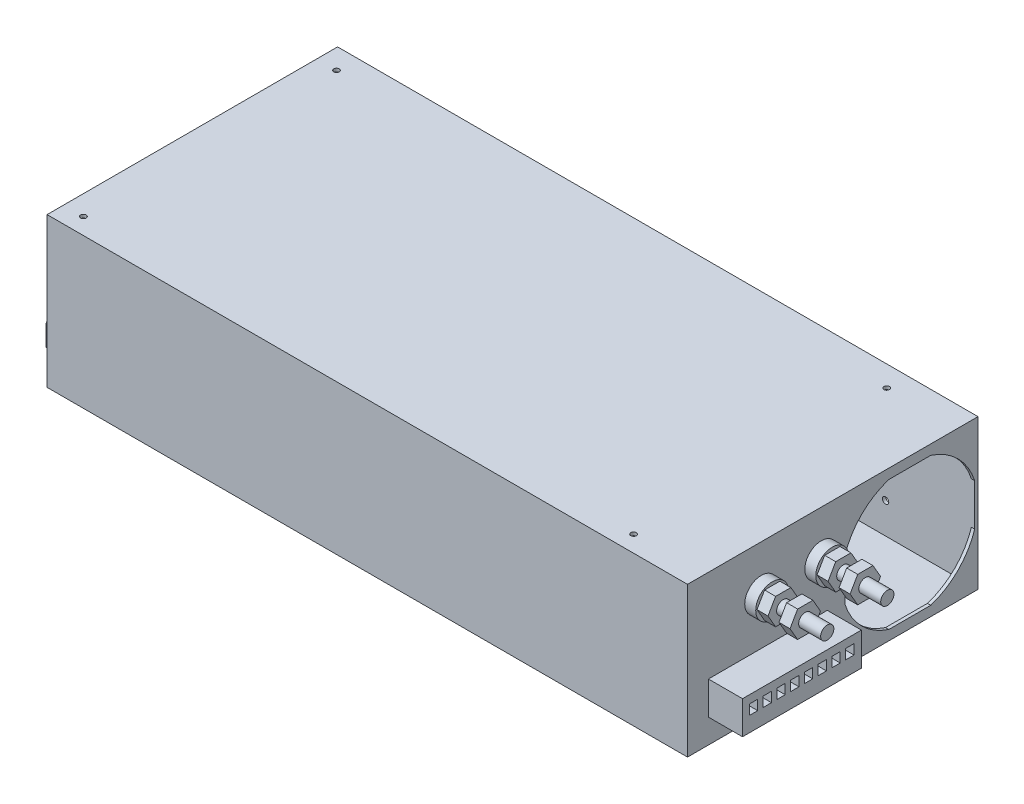
SolidWorks part; units mm, degrees
ref_plane "Front Plane" through (0, 0, 0) normal (0, 0, 1) x (1, 0, 0)
ref_plane "Top Plane" through (0, 0, 0) normal (0, 1, 0) x (1, 0, 0)
ref_plane "Right Plane" through (0, 0, 0) normal (1, 0, 0) x (0, 0, -1)
sketch "Sketch1" plane through (0, 0, 0) normal (0, 1, 0) x (1, 0, 0)
  line L1 (-145.5, -66) -> (145.5, -66)
  line L2 (-145.5, -66) -> (-145.5, 66)
  line L3 (-145.5, 66) -> (145.5, 66)
  line L4 (145.5, -66) -> (145.5, 66)
  line L5 (0, 66) -> (0, -66) construction
  line L6 (-145.5, 0) -> (145.5, 0) construction
  line L7 (-136.5, 56.5) -> (113.5, 56.5) construction
  line L8 (-136.5, 56.5) -> (-136.5, -58.5) construction
  line L9 (-136.5, -58.5) -> (113.5, -58.5) construction
  line L10 (113.5, 56.5) -> (113.5, -58.5) construction
  line L11 (-11.5, -58.5) -> (-11.5, 56.5) construction
  line L12 (-136.5, -1) -> (113.5, -1) construction
  circle A0 centre (-136.5, 56.5) radius 1.5 construction
  circle A1 centre (113.5, 56.5) radius 1.5 construction
  circle A2 centre (113.5, -58.5) radius 1.5 construction
  circle A3 centre (-136.5, -58.5) radius 1.5 construction
  point P0 (0, 0)
  point P181 (-11.5, -1)
  dimension "D3" = 32
  dimension "D4" = 3
  dimension "D6" = 250
  dimension "D7" = 115
  dimension "D1" = 291
  dimension "D2" = 132
  dimension "D5" = 9.5
extrude "Boss-Extrude1" add sketch "Sketch1" along normal blind 68
sketch "Sketch2" plane through (0, 0, 0) normal (0, -1, 0) x (-1, 0, 0)
  line L0 (-50.3392, -42.885) -> (382.3274, -42.885) construction
  line L1 (-49.7856, -55.3048) -> (382.8811, -55.3048) construction
sketch "Sketch4" plane through (145.5, 0, 0) normal (1, 0, 0) x (0, 0, -1)
  line L0 (-7.9676, 299.7952) -> (184.6991, 299.7952) construction
sketch "Sketch5" plane through (-145.5, 0, 0) normal (-1, 0, 0) x (0, 0, 1)
  line L0 (404.3119, 214.2342) -> (558.9785, 214.2342) construction
sketch "Sketch6" plane through (0, 0, -66) normal (0, 0, -1) x (-1, 0, 0)
  line L0 (145.5, 34) -> (-145.5, 34) construction
  line L1 (145.5, 68) -> (145.5, 0) construction
  line L2 (-145.5, 68) -> (-145.5, 0) construction
  line L3 (-145.5, 68) -> (145.5, 68) construction
  line L4 (-95, 15.5) -> (104.5, 15.5) construction
  line L5 (-95, 15.5) -> (-95, 52.5) construction
  line L6 (-95, 52.5) -> (104.5, 52.5) construction
  line L7 (104.5, 15.5) -> (104.5, 52.5) construction
  line L8 (4.75, 52.5) -> (4.75, 15.5) construction
  line L9 (-95, 34) -> (104.5, 34) construction
  point P6 (4.75, 34)
  point P12 (95, 52.5)
  point P13 (95, 15.5)
  point P17 (-105, 52.5)
  point P18 (-105, 15.5)
  dimension "D1" = 15.5
  dimension "D2" = 41
  dimension "D3" = 199.5
  dimension "D4" = 50.5
  dimension "D6" = 200
  dimension "D5" = 2
shell "Shell1" thickness 1.5
hole_wizard "M3x0.5 Tapped Hole1" positions "Sketch8" profile "Sketch9" tap size "M3x0.5" standard "ANSI Metric"
sketch "Sketch8" plane through (0, 68, 0) normal (0, 1, 0) x (1, 0, 0)
  point P0 (-136.5, 56.5)
  point P3 (-136.5, -58.5)
  point P6 (113.5, -58.5)
  point P9 (113.5, 56.5)
sketch "Sketch9" plane through (-136.5, 68, -56.5) normal (1, 0, 0) x (0, 0, 1)
  line L0 (0, 0) -> (0, 8.2511)
  line L1 (0, 8.2511) -> (1.25, 7.5)
  line L2 (1.25, 7.5) -> (1.25, 0)
  line L5 (1.25, 0) -> (0, 0)
  line L10 (0, 8.2511) -> (-1.25, 7.5) construction
  line L11 (0, -6.35) -> (0, 107.95) construction
  dimension "Tap Drill Dia." = 2.5
  dimension "Tap Drill Depth" = 7.5
  dimension "Drill Angle" = 118
cosmetic thread "Hole Thread1" parameters "D1"=1.5, "D2"=3
cosmetic thread "Hole Thread2" parameters "D1"=1.5, "D2"=3
cosmetic thread "Hole Thread3" parameters "D1"=1.5, "D2"=3
cosmetic thread "Hole Thread4" parameters "D1"=1.5, "D2"=3
sketch "Sketch10" plane through (0, 0, 0) normal (0, -1, 0) x (1, 0, 0)
  line L0 (-131.25, -60.5) -> (-115.25, -60.5) construction
  line L1 (-131.25, -59) -> (-115.25, -59)
  line L2 (-131.25, -62) -> (-115.25, -62)
  line L3 (-145.5, -66) -> (145.5, -66) construction
  line L4 (-145.5, 66) -> (-145.5, -66) construction
  line L5 (-104.75, -60.5) -> (-88.75, -60.5) construction
  line L6 (-104.75, -59) -> (-88.75, -59)
  line L7 (-104.75, -62) -> (-88.75, -62)
  line L8 (-104.75, -55.5) -> (-88.75, -55.5) construction
  line L9 (-104.75, -54) -> (-88.75, -54)
  line L10 (-104.75, -57) -> (-88.75, -57)
  line L11 (-104.75, -50.5) -> (-88.75, -50.5) construction
  line L12 (-104.75, -49) -> (-88.75, -49)
  line L13 (-104.75, -52) -> (-88.75, -52)
  line L14 (-104.75, -45.5) -> (-88.75, -45.5) construction
  line L15 (-104.75, -44) -> (-88.75, -44)
  line L16 (-104.75, -47) -> (-88.75, -47)
  line L17 (-104.75, -40.5) -> (-88.75, -40.5) construction
  line L18 (-104.75, -39) -> (-88.75, -39)
  line L19 (-104.75, -42) -> (-88.75, -42)
  line L20 (-104.75, -35.5) -> (-88.75, -35.5) construction
  line L21 (-104.75, -34) -> (-88.75, -34)
  line L22 (-104.75, -37) -> (-88.75, -37)
  line L23 (-104.75, -30.5) -> (-88.75, -30.5) construction
  line L24 (-104.75, -29) -> (-88.75, -29)
  line L25 (-104.75, -32) -> (-88.75, -32)
  line L26 (-104.75, -25.5) -> (-88.75, -25.5) construction
  line L27 (-104.75, -24) -> (-88.75, -24)
  line L28 (-104.75, -27) -> (-88.75, -27)
  line L29 (-104.75, -20.5) -> (-88.75, -20.5) construction
  line L30 (-104.75, -19) -> (-88.75, -19)
  line L31 (-104.75, -22) -> (-88.75, -22)
  line L32 (-104.75, -15.5) -> (-88.75, -15.5) construction
  line L33 (-104.75, -14) -> (-88.75, -14)
  line L34 (-104.75, -17) -> (-88.75, -17)
  line L35 (-104.75, -10.5) -> (-88.75, -10.5) construction
  line L36 (-104.75, -9) -> (-88.75, -9)
  line L37 (-104.75, -12) -> (-88.75, -12)
  line L38 (-104.75, -5.5) -> (-88.75, -5.5) construction
  line L39 (-104.75, -4) -> (-88.75, -4)
  line L40 (-104.75, -7) -> (-88.75, -7)
  line L41 (-104.75, -0.5) -> (-88.75, -0.5) construction
  line L42 (-104.75, 1) -> (-88.75, 1)
  line L43 (-104.75, -2) -> (-88.75, -2)
  line L44 (-104.75, 4.5) -> (-88.75, 4.5) construction
  line L45 (-104.75, 6) -> (-88.75, 6)
  line L46 (-104.75, 3) -> (-88.75, 3)
  line L47 (-104.75, 9.5) -> (-88.75, 9.5) construction
  line L48 (-104.75, 11) -> (-88.75, 11)
  line L49 (-104.75, 8) -> (-88.75, 8)
  line L50 (-104.75, 14.5) -> (-88.75, 14.5) construction
  line L51 (-104.75, 16) -> (-88.75, 16)
  line L52 (-104.75, 13) -> (-88.75, 13)
  line L53 (-104.75, 19.5) -> (-88.75, 19.5) construction
  line L54 (-104.75, 21) -> (-88.75, 21)
  line L55 (-104.75, 18) -> (-88.75, 18)
  line L56 (-104.75, 24.5) -> (-88.75, 24.5) construction
  line L57 (-104.75, 26) -> (-88.75, 26)
  line L58 (-104.75, 23) -> (-88.75, 23)
  line L59 (-104.75, 29.5) -> (-88.75, 29.5) construction
  line L60 (-104.75, 31) -> (-88.75, 31)
  line L61 (-104.75, 28) -> (-88.75, 28)
  line L62 (-104.75, 34.5) -> (-88.75, 34.5) construction
  line L63 (-104.75, 36) -> (-88.75, 36)
  line L64 (-104.75, 33) -> (-88.75, 33)
  line L65 (-104.75, 39.5) -> (-88.75, 39.5) construction
  line L66 (-104.75, 41) -> (-88.75, 41)
  line L67 (-104.75, 38) -> (-88.75, 38)
  line L68 (-104.75, 44.5) -> (-88.75, 44.5) construction
  line L69 (-104.75, 46) -> (-88.75, 46)
  line L70 (-104.75, 43) -> (-88.75, 43)
  line L71 (-104.75, 49.5) -> (-88.75, 49.5) construction
  line L72 (-104.75, 51) -> (-88.75, 51)
  line L73 (-104.75, 48) -> (-88.75, 48)
  line L74 (-104.75, 54.5) -> (-88.75, 54.5) construction
  line L75 (-104.75, 56) -> (-88.75, 56)
  line L76 (-104.75, 53) -> (-88.75, 53)
  line L77 (-104.75, 59.5) -> (-88.75, 59.5) construction
  line L78 (-104.75, 61) -> (-88.75, 61)
  line L79 (-104.75, 58) -> (-88.75, 58)
  line L80 (-131.25, -55.5) -> (-115.25, -55.5) construction
  line L81 (-131.25, -54) -> (-115.25, -54)
  line L82 (-131.25, -57) -> (-115.25, -57)
  line L83 (-131.25, -50.5) -> (-115.25, -50.5) construction
  line L84 (-131.25, -49) -> (-115.25, -49)
  line L85 (-131.25, -52) -> (-115.25, -52)
  line L86 (-131.25, -45.5) -> (-115.25, -45.5) construction
  line L87 (-131.25, -44) -> (-115.25, -44)
  line L88 (-131.25, -47) -> (-115.25, -47)
  line L89 (-131.25, -40.5) -> (-115.25, -40.5) construction
  line L90 (-131.25, -39) -> (-115.25, -39)
  line L91 (-131.25, -42) -> (-115.25, -42)
  line L92 (-131.25, -35.5) -> (-115.25, -35.5) construction
  line L93 (-131.25, -34) -> (-115.25, -34)
  line L94 (-131.25, -37) -> (-115.25, -37)
  line L95 (-131.25, -30.5) -> (-115.25, -30.5) construction
  line L96 (-131.25, -29) -> (-115.25, -29)
  line L97 (-131.25, -32) -> (-115.25, -32)
  line L98 (-131.25, -25.5) -> (-115.25, -25.5) construction
  line L99 (-131.25, -24) -> (-115.25, -24)
  line L100 (-131.25, -27) -> (-115.25, -27)
  line L101 (-131.25, -20.5) -> (-115.25, -20.5) construction
  line L102 (-131.25, -19) -> (-115.25, -19)
  line L103 (-131.25, -22) -> (-115.25, -22)
  line L104 (-131.25, -15.5) -> (-115.25, -15.5) construction
  line L105 (-131.25, -14) -> (-115.25, -14)
  line L106 (-131.25, -17) -> (-115.25, -17)
  line L107 (-131.25, -10.5) -> (-115.25, -10.5) construction
  line L108 (-131.25, -9) -> (-115.25, -9)
  line L109 (-131.25, -12) -> (-115.25, -12)
  line L110 (-131.25, -5.5) -> (-115.25, -5.5) construction
  line L111 (-131.25, -4) -> (-115.25, -4)
  line L112 (-131.25, -7) -> (-115.25, -7)
  line L113 (-131.25, -0.5) -> (-115.25, -0.5) construction
  line L114 (-131.25, 1) -> (-115.25, 1)
  line L115 (-131.25, -2) -> (-115.25, -2)
  line L116 (-131.25, 4.5) -> (-115.25, 4.5) construction
  line L117 (-131.25, 6) -> (-115.25, 6)
  line L118 (-131.25, 3) -> (-115.25, 3)
  line L119 (-131.25, 9.5) -> (-115.25, 9.5) construction
  line L120 (-131.25, 11) -> (-115.25, 11)
  line L121 (-131.25, 8) -> (-115.25, 8)
  line L122 (-131.25, 14.5) -> (-115.25, 14.5) construction
  line L123 (-131.25, 16) -> (-115.25, 16)
  line L124 (-131.25, 13) -> (-115.25, 13)
  line L125 (-131.25, 19.5) -> (-115.25, 19.5) construction
  line L126 (-131.25, 21) -> (-115.25, 21)
  line L127 (-131.25, 18) -> (-115.25, 18)
  line L128 (-131.25, 24.5) -> (-115.25, 24.5) construction
  line L129 (-131.25, 26) -> (-115.25, 26)
  line L130 (-131.25, 23) -> (-115.25, 23)
  line L131 (-131.25, 29.5) -> (-115.25, 29.5) construction
  line L132 (-131.25, 31) -> (-115.25, 31)
  line L133 (-131.25, 28) -> (-115.25, 28)
  line L134 (-131.25, 34.5) -> (-115.25, 34.5) construction
  line L135 (-131.25, 36) -> (-115.25, 36)
  line L136 (-131.25, 33) -> (-115.25, 33)
  line L137 (-131.25, 39.5) -> (-115.25, 39.5) construction
  line L138 (-131.25, 41) -> (-115.25, 41)
  line L139 (-131.25, 38) -> (-115.25, 38)
  line L140 (-131.25, 44.5) -> (-115.25, 44.5) construction
  line L141 (-131.25, 46) -> (-115.25, 46)
  line L142 (-131.25, 43) -> (-115.25, 43)
  line L143 (-131.25, 49.5) -> (-115.25, 49.5) construction
  line L144 (-131.25, 51) -> (-115.25, 51)
  line L145 (-131.25, 48) -> (-115.25, 48)
  line L146 (-131.25, 54.5) -> (-115.25, 54.5) construction
  line L147 (-131.25, 56) -> (-115.25, 56)
  line L148 (-131.25, 53) -> (-115.25, 53)
  line L149 (-131.25, 59.5) -> (-115.25, 59.5) construction
  line L150 (-131.25, 61) -> (-115.25, 61)
  line L151 (-131.25, 58) -> (-115.25, 58)
  arc A0 (-131.25, -59) -> (-131.25, -62) centre (-131.25, -60.5) ccw
  arc A1 (-115.25, -62) -> (-115.25, -59) centre (-115.25, -60.5) ccw
  arc A2 (-104.75, -59) -> (-104.75, -62) centre (-104.75, -60.5) ccw
  arc A3 (-88.75, -62) -> (-88.75, -59) centre (-88.75, -60.5) ccw
  arc A4 (-104.75, -54) -> (-104.75, -57) centre (-104.75, -55.5) ccw
  arc A5 (-88.75, -57) -> (-88.75, -54) centre (-88.75, -55.5) ccw
  arc A6 (-104.75, -49) -> (-104.75, -52) centre (-104.75, -50.5) ccw
  arc A7 (-88.75, -52) -> (-88.75, -49) centre (-88.75, -50.5) ccw
  arc A8 (-104.75, -44) -> (-104.75, -47) centre (-104.75, -45.5) ccw
  arc A9 (-88.75, -47) -> (-88.75, -44) centre (-88.75, -45.5) ccw
  arc A10 (-104.75, -39) -> (-104.75, -42) centre (-104.75, -40.5) ccw
  arc A11 (-88.75, -42) -> (-88.75, -39) centre (-88.75, -40.5) ccw
  arc A12 (-104.75, -34) -> (-104.75, -37) centre (-104.75, -35.5) ccw
  arc A13 (-88.75, -37) -> (-88.75, -34) centre (-88.75, -35.5) ccw
  arc A14 (-104.75, -29) -> (-104.75, -32) centre (-104.75, -30.5) ccw
  arc A15 (-88.75, -32) -> (-88.75, -29) centre (-88.75, -30.5) ccw
  arc A16 (-104.75, -24) -> (-104.75, -27) centre (-104.75, -25.5) ccw
  arc A17 (-88.75, -27) -> (-88.75, -24) centre (-88.75, -25.5) ccw
  arc A18 (-104.75, -19) -> (-104.75, -22) centre (-104.75, -20.5) ccw
  arc A19 (-88.75, -22) -> (-88.75, -19) centre (-88.75, -20.5) ccw
  arc A20 (-104.75, -14) -> (-104.75, -17) centre (-104.75, -15.5) ccw
  arc A21 (-88.75, -17) -> (-88.75, -14) centre (-88.75, -15.5) ccw
  arc A22 (-104.75, -9) -> (-104.75, -12) centre (-104.75, -10.5) ccw
  arc A23 (-88.75, -12) -> (-88.75, -9) centre (-88.75, -10.5) ccw
  arc A24 (-104.75, -4) -> (-104.75, -7) centre (-104.75, -5.5) ccw
  arc A25 (-88.75, -7) -> (-88.75, -4) centre (-88.75, -5.5) ccw
  arc A26 (-104.75, 1) -> (-104.75, -2) centre (-104.75, -0.5) ccw
  arc A27 (-88.75, -2) -> (-88.75, 1) centre (-88.75, -0.5) ccw
  arc A28 (-104.75, 6) -> (-104.75, 3) centre (-104.75, 4.5) ccw
  arc A29 (-88.75, 3) -> (-88.75, 6) centre (-88.75, 4.5) ccw
  arc A30 (-104.75, 11) -> (-104.75, 8) centre (-104.75, 9.5) ccw
  arc A31 (-88.75, 8) -> (-88.75, 11) centre (-88.75, 9.5) ccw
  arc A32 (-104.75, 16) -> (-104.75, 13) centre (-104.75, 14.5) ccw
  arc A33 (-88.75, 13) -> (-88.75, 16) centre (-88.75, 14.5) ccw
  arc A34 (-104.75, 21) -> (-104.75, 18) centre (-104.75, 19.5) ccw
  arc A35 (-88.75, 18) -> (-88.75, 21) centre (-88.75, 19.5) ccw
  arc A36 (-104.75, 26) -> (-104.75, 23) centre (-104.75, 24.5) ccw
  arc A37 (-88.75, 23) -> (-88.75, 26) centre (-88.75, 24.5) ccw
  arc A38 (-104.75, 31) -> (-104.75, 28) centre (-104.75, 29.5) ccw
  arc A39 (-88.75, 28) -> (-88.75, 31) centre (-88.75, 29.5) ccw
  arc A40 (-104.75, 36) -> (-104.75, 33) centre (-104.75, 34.5) ccw
  arc A41 (-88.75, 33) -> (-88.75, 36) centre (-88.75, 34.5) ccw
  arc A42 (-104.75, 41) -> (-104.75, 38) centre (-104.75, 39.5) ccw
  arc A43 (-88.75, 38) -> (-88.75, 41) centre (-88.75, 39.5) ccw
  arc A44 (-104.75, 46) -> (-104.75, 43) centre (-104.75, 44.5) ccw
  arc A45 (-88.75, 43) -> (-88.75, 46) centre (-88.75, 44.5) ccw
  arc A46 (-104.75, 51) -> (-104.75, 48) centre (-104.75, 49.5) ccw
  arc A47 (-88.75, 48) -> (-88.75, 51) centre (-88.75, 49.5) ccw
  arc A48 (-104.75, 56) -> (-104.75, 53) centre (-104.75, 54.5) ccw
  arc A49 (-88.75, 53) -> (-88.75, 56) centre (-88.75, 54.5) ccw
  arc A50 (-104.75, 61) -> (-104.75, 58) centre (-104.75, 59.5) ccw
  arc A51 (-88.75, 58) -> (-88.75, 61) centre (-88.75, 59.5) ccw
  arc A52 (-131.25, -54) -> (-131.25, -57) centre (-131.25, -55.5) ccw
  arc A53 (-115.25, -57) -> (-115.25, -54) centre (-115.25, -55.5) ccw
  arc A54 (-131.25, -49) -> (-131.25, -52) centre (-131.25, -50.5) ccw
  arc A55 (-115.25, -52) -> (-115.25, -49) centre (-115.25, -50.5) ccw
  arc A56 (-131.25, -44) -> (-131.25, -47) centre (-131.25, -45.5) ccw
  arc A57 (-115.25, -47) -> (-115.25, -44) centre (-115.25, -45.5) ccw
  arc A58 (-131.25, -39) -> (-131.25, -42) centre (-131.25, -40.5) ccw
  arc A59 (-115.25, -42) -> (-115.25, -39) centre (-115.25, -40.5) ccw
  arc A60 (-131.25, -34) -> (-131.25, -37) centre (-131.25, -35.5) ccw
  arc A61 (-115.25, -37) -> (-115.25, -34) centre (-115.25, -35.5) ccw
  arc A62 (-131.25, -29) -> (-131.25, -32) centre (-131.25, -30.5) ccw
  arc A63 (-115.25, -32) -> (-115.25, -29) centre (-115.25, -30.5) ccw
  arc A64 (-131.25, -24) -> (-131.25, -27) centre (-131.25, -25.5) ccw
  arc A65 (-115.25, -27) -> (-115.25, -24) centre (-115.25, -25.5) ccw
  arc A66 (-131.25, -19) -> (-131.25, -22) centre (-131.25, -20.5) ccw
  arc A67 (-115.25, -22) -> (-115.25, -19) centre (-115.25, -20.5) ccw
  arc A68 (-131.25, -14) -> (-131.25, -17) centre (-131.25, -15.5) ccw
  arc A69 (-115.25, -17) -> (-115.25, -14) centre (-115.25, -15.5) ccw
  arc A70 (-131.25, -9) -> (-131.25, -12) centre (-131.25, -10.5) ccw
  arc A71 (-115.25, -12) -> (-115.25, -9) centre (-115.25, -10.5) ccw
  arc A72 (-131.25, -4) -> (-131.25, -7) centre (-131.25, -5.5) ccw
  arc A73 (-115.25, -7) -> (-115.25, -4) centre (-115.25, -5.5) ccw
  arc A74 (-131.25, 1) -> (-131.25, -2) centre (-131.25, -0.5) ccw
  arc A75 (-115.25, -2) -> (-115.25, 1) centre (-115.25, -0.5) ccw
  arc A76 (-131.25, 6) -> (-131.25, 3) centre (-131.25, 4.5) ccw
  arc A77 (-115.25, 3) -> (-115.25, 6) centre (-115.25, 4.5) ccw
  arc A78 (-131.25, 11) -> (-131.25, 8) centre (-131.25, 9.5) ccw
  arc A79 (-115.25, 8) -> (-115.25, 11) centre (-115.25, 9.5) ccw
  arc A80 (-131.25, 16) -> (-131.25, 13) centre (-131.25, 14.5) ccw
  arc A81 (-115.25, 13) -> (-115.25, 16) centre (-115.25, 14.5) ccw
  arc A82 (-131.25, 21) -> (-131.25, 18) centre (-131.25, 19.5) ccw
  arc A83 (-115.25, 18) -> (-115.25, 21) centre (-115.25, 19.5) ccw
  arc A84 (-131.25, 26) -> (-131.25, 23) centre (-131.25, 24.5) ccw
  arc A85 (-115.25, 23) -> (-115.25, 26) centre (-115.25, 24.5) ccw
  arc A86 (-131.25, 31) -> (-131.25, 28) centre (-131.25, 29.5) ccw
  arc A87 (-115.25, 28) -> (-115.25, 31) centre (-115.25, 29.5) ccw
  arc A88 (-131.25, 36) -> (-131.25, 33) centre (-131.25, 34.5) ccw
  arc A89 (-115.25, 33) -> (-115.25, 36) centre (-115.25, 34.5) ccw
  arc A90 (-131.25, 41) -> (-131.25, 38) centre (-131.25, 39.5) ccw
  arc A91 (-115.25, 38) -> (-115.25, 41) centre (-115.25, 39.5) ccw
  arc A92 (-131.25, 46) -> (-131.25, 43) centre (-131.25, 44.5) ccw
  arc A93 (-115.25, 43) -> (-115.25, 46) centre (-115.25, 44.5) ccw
  arc A94 (-131.25, 51) -> (-131.25, 48) centre (-131.25, 49.5) ccw
  arc A95 (-115.25, 48) -> (-115.25, 51) centre (-115.25, 49.5) ccw
  arc A96 (-131.25, 56) -> (-131.25, 53) centre (-131.25, 54.5) ccw
  arc A97 (-115.25, 53) -> (-115.25, 56) centre (-115.25, 54.5) ccw
  arc A98 (-131.25, 61) -> (-131.25, 58) centre (-131.25, 59.5) ccw
  arc A99 (-115.25, 58) -> (-115.25, 61) centre (-115.25, 59.5) ccw
  point P2 (-123.25, -60.5)
  point P15 (-96.75, -60.5)
  point P22 (-96.75, -55.5)
  point P29 (-96.75, -50.5)
  point P36 (-96.75, -45.5)
  point P43 (-96.75, -40.5)
  point P50 (-96.75, -35.5)
  point P57 (-96.75, -30.5)
  point P64 (-96.75, -25.5)
  point P71 (-96.75, -20.5)
  point P78 (-96.75, -15.5)
  point P85 (-96.75, -10.5)
  point P92 (-96.75, -5.5)
  point P99 (-96.75, -0.5)
  point P106 (-96.75, 4.5)
  point P113 (-96.75, 9.5)
  point P120 (-96.75, 14.5)
  point P127 (-96.75, 19.5)
  point P134 (-96.75, 24.5)
  point P141 (-96.75, 29.5)
  point P148 (-96.75, 34.5)
  point P155 (-96.75, 39.5)
  point P162 (-96.75, 44.5)
  point P169 (-96.75, 49.5)
  point P176 (-96.75, 54.5)
  point P183 (-96.75, 59.5)
  point P190 (-123.25, -55.5)
  point P197 (-123.25, -50.5)
  point P204 (-123.25, -45.5)
  point P211 (-123.25, -40.5)
  point P218 (-123.25, -35.5)
  point P225 (-123.25, -30.5)
  point P232 (-123.25, -25.5)
  point P239 (-123.25, -20.5)
  point P246 (-123.25, -15.5)
  point P253 (-123.25, -10.5)
  point P260 (-123.25, -5.5)
  point P267 (-123.25, -0.5)
  point P274 (-123.25, 4.5)
  point P281 (-123.25, 9.5)
  point P288 (-123.25, 14.5)
  point P295 (-123.25, 19.5)
  point P302 (-123.25, 24.5)
  point P309 (-123.25, 29.5)
  point P316 (-123.25, 34.5)
  point P323 (-123.25, 39.5)
  point P330 (-123.25, 44.5)
  point P337 (-123.25, 49.5)
  point P344 (-123.25, 54.5)
  point P351 (-123.25, 59.5)
  dimension "D1" = 1.5
  dimension "D7" = 26.5
  dimension "D8" = 5
  dimension "D2" = 16
  dimension "D3" = 5.5
  dimension "D4" = 14.25
  dimension "D5" = 2
  dimension "D6" = 25
extrude "Cut-Extrude1" cut sketch "Sketch10" against normal up to next (1.5 mm away)
sketch "Sketch11" plane through (-145.5, 0, 0) normal (-1, 0, 0) x (0, 0, 1)
  line L0 (-66, 0) -> (66, 0) construction
  line L1 (60, 10) -> (50, 10)
  line L2 (60, 10) -> (60, 21.5)
  line L3 (60, 21.5) -> (50, 21.5)
  line L4 (50, 10) -> (50, 21.5)
  line L5 (55, 21.5) -> (55, 10) construction
  line L6 (60, 15.75) -> (50, 15.75) construction
  line L7 (66, 68) -> (66, 0) construction
  line L8 (50, 10) -> (40, 10)
  line L9 (40, 10) -> (40, 21.5)
  line L10 (50, 21.5) -> (40, 21.5)
  line L11 (40, 10) -> (30, 10)
  line L12 (30, 10) -> (30, 21.5)
  line L13 (40, 21.5) -> (30, 21.5)
  line L14 (30, 10) -> (20, 10)
  line L15 (20, 10) -> (20, 21.5)
  line L16 (30, 21.5) -> (20, 21.5)
  line L17 (20, 10) -> (10, 10)
  line L18 (10, 10) -> (10, 21.5)
  line L19 (20, 21.5) -> (10, 21.5)
  line L20 (16, 21.5) -> (16, 26.5)
  line L21 (60, 10) -> (61.5, 10)
  line L22 (60, 10) -> (60, 21.5)
  line L23 (60, 21.5) -> (61.5, 21.5)
  line L24 (61.5, 10) -> (61.5, 21.5)
  line L25 (60.75, 21.5) -> (60.75, 10) construction
  line L26 (60, 15.75) -> (61.5, 15.75) construction
  line L27 (10, 10) -> (8.5, 10)
  line L28 (10, 10) -> (10, 21.5)
  line L29 (10, 21.5) -> (8.5, 21.5)
  line L30 (8.5, 10) -> (8.5, 21.5)
  line L31 (9.25, 21.5) -> (9.25, 10) construction
  line L32 (10, 15.75) -> (8.5, 15.75) construction
  line L33 (16, 10) -> (54, 10)
  line L34 (16, 10) -> (16, 5)
  line L35 (19, 2) -> (51, 2)
  line L36 (54, 10) -> (54, 5)
  line L37 (35, 2) -> (35, 10) construction
  line L38 (16, 7.5) -> (54, 7.5) construction
  line L39 (19, 29.5) -> (51, 29.5)
  line L40 (54, 21.5) -> (54, 26.5)
  line L41 (2, 11.75) -> (2, 27.75) construction
  line L42 (0.5, 11.75) -> (0.5, 27.75)
  line L43 (3.5, 11.75) -> (3.5, 27.75)
  line L44 (-3, 11.75) -> (-3, 27.75) construction
  line L45 (-4.5, 11.75) -> (-4.5, 27.75)
  line L46 (-1.5, 11.75) -> (-1.5, 27.75)
  line L47 (-8, 11.75) -> (-8, 27.75) construction
  line L48 (-9.5, 11.75) -> (-9.5, 27.75)
  line L49 (-6.5, 11.75) -> (-6.5, 27.75)
  line L50 (-13, 11.75) -> (-13, 27.75) construction
  line L51 (-14.5, 11.75) -> (-14.5, 27.75)
  line L52 (-11.5, 11.75) -> (-11.5, 27.75)
  line L53 (-18, 11.75) -> (-18, 27.75) construction
  line L54 (-19.5, 11.75) -> (-19.5, 27.75)
  line L55 (-16.5, 11.75) -> (-16.5, 27.75)
  line L56 (-23, 11.75) -> (-23, 27.75) construction
  line L57 (-24.5, 11.75) -> (-24.5, 27.75)
  line L58 (-21.5, 11.75) -> (-21.5, 27.75)
  line L59 (-28, 11.75) -> (-28, 27.75) construction
  line L60 (-29.5, 11.75) -> (-29.5, 27.75)
  line L61 (-26.5, 11.75) -> (-26.5, 27.75)
  line L62 (-33, 11.75) -> (-33, 27.75) construction
  line L63 (-34.5, 11.75) -> (-34.5, 27.75)
  line L64 (-31.5, 11.75) -> (-31.5, 27.75)
  line L65 (-38, 11.75) -> (-38, 27.75) construction
  line L66 (-39.5, 11.75) -> (-39.5, 27.75)
  line L67 (-36.5, 11.75) -> (-36.5, 27.75)
  line L68 (-43, 11.75) -> (-43, 27.75) construction
  line L69 (-44.5, 11.75) -> (-44.5, 27.75)
  line L70 (-41.5, 11.75) -> (-41.5, 27.75)
  line L71 (-48, 11.75) -> (-48, 27.75) construction
  line L72 (-49.5, 11.75) -> (-49.5, 27.75)
  line L73 (-46.5, 11.75) -> (-46.5, 27.75)
  line L74 (-53, 11.75) -> (-53, 27.75) construction
  line L75 (-54.5, 11.75) -> (-54.5, 27.75)
  line L76 (-51.5, 11.75) -> (-51.5, 27.75)
  line L77 (-58, 11.75) -> (-58, 27.75) construction
  line L78 (-59.5, 11.75) -> (-59.5, 27.75)
  line L79 (-56.5, 11.75) -> (-56.5, 27.75)
  line L80 (-66, 68) -> (-66, 0) construction
  line L81 (2, 37.25) -> (2, 53.25) construction
  line L82 (0.5, 37.25) -> (0.5, 53.25)
  line L83 (3.5, 37.25) -> (3.5, 53.25)
  line L84 (-3, 37.25) -> (-3, 53.25) construction
  line L85 (-4.5, 37.25) -> (-4.5, 53.25)
  line L86 (-1.5, 37.25) -> (-1.5, 53.25)
  line L87 (-8, 37.25) -> (-8, 53.25) construction
  line L88 (-9.5, 37.25) -> (-9.5, 53.25)
  line L89 (-6.5, 37.25) -> (-6.5, 53.25)
  line L90 (-13, 37.25) -> (-13, 53.25) construction
  line L91 (-14.5, 37.25) -> (-14.5, 53.25)
  line L92 (-11.5, 37.25) -> (-11.5, 53.25)
  line L93 (-18, 37.25) -> (-18, 53.25) construction
  line L94 (-19.5, 37.25) -> (-19.5, 53.25)
  line L95 (-16.5, 37.25) -> (-16.5, 53.25)
  line L96 (-23, 37.25) -> (-23, 53.25) construction
  line L97 (-24.5, 37.25) -> (-24.5, 53.25)
  line L98 (-21.5, 37.25) -> (-21.5, 53.25)
  line L99 (-28, 37.25) -> (-28, 53.25) construction
  line L100 (-29.5, 37.25) -> (-29.5, 53.25)
  line L101 (-26.5, 37.25) -> (-26.5, 53.25)
  line L102 (-33, 37.25) -> (-33, 53.25) construction
  line L103 (-34.5, 37.25) -> (-34.5, 53.25)
  line L104 (-31.5, 37.25) -> (-31.5, 53.25)
  line L105 (-38, 37.25) -> (-38, 53.25) construction
  line L106 (-39.5, 37.25) -> (-39.5, 53.25)
  line L107 (-36.5, 37.25) -> (-36.5, 53.25)
  line L108 (-43, 37.25) -> (-43, 53.25) construction
  line L109 (-44.5, 37.25) -> (-44.5, 53.25)
  line L110 (-41.5, 37.25) -> (-41.5, 53.25)
  line L111 (-48, 37.25) -> (-48, 53.25) construction
  line L112 (-49.5, 37.25) -> (-49.5, 53.25)
  line L113 (-46.5, 37.25) -> (-46.5, 53.25)
  line L114 (7, 37.25) -> (7, 53.25) construction
  line L115 (5.5, 37.25) -> (5.5, 53.25)
  line L116 (8.5, 37.25) -> (8.5, 53.25)
  line L117 (12, 37.25) -> (12, 53.25) construction
  line L118 (10.5, 37.25) -> (10.5, 53.25)
  line L119 (13.5, 37.25) -> (13.5, 53.25)
  line L120 (17, 37.25) -> (17, 53.25) construction
  line L121 (15.5, 37.25) -> (15.5, 53.25)
  line L122 (18.5, 37.25) -> (18.5, 53.25)
  line L123 (22, 37.25) -> (22, 53.25) construction
  line L124 (20.5, 37.25) -> (20.5, 53.25)
  line L125 (23.5, 37.25) -> (23.5, 53.25)
  line L126 (27, 37.25) -> (27, 53.25) construction
  line L127 (25.5, 37.25) -> (25.5, 53.25)
  line L128 (28.5, 37.25) -> (28.5, 53.25)
  line L129 (32, 37.25) -> (32, 53.25) construction
  line L130 (30.5, 37.25) -> (30.5, 53.25)
  line L131 (33.5, 37.25) -> (33.5, 53.25)
  line L132 (37, 37.25) -> (37, 53.25) construction
  line L133 (35.5, 37.25) -> (35.5, 53.25)
  line L134 (38.5, 37.25) -> (38.5, 53.25)
  line L135 (42, 37.25) -> (42, 53.25) construction
  line L136 (40.5, 37.25) -> (40.5, 53.25)
  line L137 (43.5, 37.25) -> (43.5, 53.25)
  line L138 (47, 37.25) -> (47, 53.25) construction
  line L139 (45.5, 37.25) -> (45.5, 53.25)
  line L140 (48.5, 37.25) -> (48.5, 53.25)
  line L141 (52, 37.25) -> (52, 53.25) construction
  line L142 (50.5, 37.25) -> (50.5, 53.25)
  line L143 (53.5, 37.25) -> (53.5, 53.25)
  arc A0 (16, 5) -> (19, 2) centre (19, 5) ccw
  arc A1 (51, 2) -> (54, 5) centre (51, 5) ccw
  arc A2 (16, 26.5) -> (19, 29.5) centre (19, 26.5) cw
  arc A3 (51, 29.5) -> (54, 26.5) centre (51, 26.5) cw
  arc A4 (0.5, 11.75) -> (3.5, 11.75) centre (2, 11.75) ccw
  arc A5 (3.5, 27.75) -> (0.5, 27.75) centre (2, 27.75) ccw
  arc A6 (-4.5, 11.75) -> (-1.5, 11.75) centre (-3, 11.75) ccw
  arc A7 (-1.5, 27.75) -> (-4.5, 27.75) centre (-3, 27.75) ccw
  arc A8 (-9.5, 11.75) -> (-6.5, 11.75) centre (-8, 11.75) ccw
  arc A9 (-6.5, 27.75) -> (-9.5, 27.75) centre (-8, 27.75) ccw
  arc A10 (-14.5, 11.75) -> (-11.5, 11.75) centre (-13, 11.75) ccw
  arc A11 (-11.5, 27.75) -> (-14.5, 27.75) centre (-13, 27.75) ccw
  arc A12 (-19.5, 11.75) -> (-16.5, 11.75) centre (-18, 11.75) ccw
  arc A13 (-16.5, 27.75) -> (-19.5, 27.75) centre (-18, 27.75) ccw
  arc A14 (-24.5, 11.75) -> (-21.5, 11.75) centre (-23, 11.75) ccw
  arc A15 (-21.5, 27.75) -> (-24.5, 27.75) centre (-23, 27.75) ccw
  arc A16 (-29.5, 11.75) -> (-26.5, 11.75) centre (-28, 11.75) ccw
  arc A17 (-26.5, 27.75) -> (-29.5, 27.75) centre (-28, 27.75) ccw
  arc A18 (-34.5, 11.75) -> (-31.5, 11.75) centre (-33, 11.75) ccw
  arc A19 (-31.5, 27.75) -> (-34.5, 27.75) centre (-33, 27.75) ccw
  arc A20 (-39.5, 11.75) -> (-36.5, 11.75) centre (-38, 11.75) ccw
  arc A21 (-36.5, 27.75) -> (-39.5, 27.75) centre (-38, 27.75) ccw
  arc A22 (-44.5, 11.75) -> (-41.5, 11.75) centre (-43, 11.75) ccw
  arc A23 (-41.5, 27.75) -> (-44.5, 27.75) centre (-43, 27.75) ccw
  arc A24 (-49.5, 11.75) -> (-46.5, 11.75) centre (-48, 11.75) ccw
  arc A25 (-46.5, 27.75) -> (-49.5, 27.75) centre (-48, 27.75) ccw
  arc A26 (-54.5, 11.75) -> (-51.5, 11.75) centre (-53, 11.75) ccw
  arc A27 (-51.5, 27.75) -> (-54.5, 27.75) centre (-53, 27.75) ccw
  arc A28 (-59.5, 11.75) -> (-56.5, 11.75) centre (-58, 11.75) ccw
  arc A29 (-56.5, 27.75) -> (-59.5, 27.75) centre (-58, 27.75) ccw
  arc A30 (0.5, 37.25) -> (3.5, 37.25) centre (2, 37.25) ccw
  arc A31 (3.5, 53.25) -> (0.5, 53.25) centre (2, 53.25) ccw
  arc A32 (-4.5, 37.25) -> (-1.5, 37.25) centre (-3, 37.25) ccw
  arc A33 (-1.5, 53.25) -> (-4.5, 53.25) centre (-3, 53.25) ccw
  arc A34 (-9.5, 37.25) -> (-6.5, 37.25) centre (-8, 37.25) ccw
  arc A35 (-6.5, 53.25) -> (-9.5, 53.25) centre (-8, 53.25) ccw
  arc A36 (-14.5, 37.25) -> (-11.5, 37.25) centre (-13, 37.25) ccw
  arc A37 (-11.5, 53.25) -> (-14.5, 53.25) centre (-13, 53.25) ccw
  arc A38 (-19.5, 37.25) -> (-16.5, 37.25) centre (-18, 37.25) ccw
  arc A39 (-16.5, 53.25) -> (-19.5, 53.25) centre (-18, 53.25) ccw
  arc A40 (-24.5, 37.25) -> (-21.5, 37.25) centre (-23, 37.25) ccw
  arc A41 (-21.5, 53.25) -> (-24.5, 53.25) centre (-23, 53.25) ccw
  arc A42 (-29.5, 37.25) -> (-26.5, 37.25) centre (-28, 37.25) ccw
  arc A43 (-26.5, 53.25) -> (-29.5, 53.25) centre (-28, 53.25) ccw
  arc A44 (-34.5, 37.25) -> (-31.5, 37.25) centre (-33, 37.25) ccw
  arc A45 (-31.5, 53.25) -> (-34.5, 53.25) centre (-33, 53.25) ccw
  arc A46 (-39.5, 37.25) -> (-36.5, 37.25) centre (-38, 37.25) ccw
  arc A47 (-36.5, 53.25) -> (-39.5, 53.25) centre (-38, 53.25) ccw
  arc A48 (-44.5, 37.25) -> (-41.5, 37.25) centre (-43, 37.25) ccw
  arc A49 (-41.5, 53.25) -> (-44.5, 53.25) centre (-43, 53.25) ccw
  arc A50 (-49.5, 37.25) -> (-46.5, 37.25) centre (-48, 37.25) ccw
  arc A51 (-46.5, 53.25) -> (-49.5, 53.25) centre (-48, 53.25) ccw
  arc A52 (5.5, 37.25) -> (8.5, 37.25) centre (7, 37.25) ccw
  arc A53 (8.5, 53.25) -> (5.5, 53.25) centre (7, 53.25) ccw
  arc A54 (10.5, 37.25) -> (13.5, 37.25) centre (12, 37.25) ccw
  arc A55 (13.5, 53.25) -> (10.5, 53.25) centre (12, 53.25) ccw
  arc A56 (15.5, 37.25) -> (18.5, 37.25) centre (17, 37.25) ccw
  arc A57 (18.5, 53.25) -> (15.5, 53.25) centre (17, 53.25) ccw
  arc A58 (20.5, 37.25) -> (23.5, 37.25) centre (22, 37.25) ccw
  arc A59 (23.5, 53.25) -> (20.5, 53.25) centre (22, 53.25) ccw
  arc A60 (25.5, 37.25) -> (28.5, 37.25) centre (27, 37.25) ccw
  arc A61 (28.5, 53.25) -> (25.5, 53.25) centre (27, 53.25) ccw
  arc A62 (30.5, 37.25) -> (33.5, 37.25) centre (32, 37.25) ccw
  arc A63 (33.5, 53.25) -> (30.5, 53.25) centre (32, 53.25) ccw
  arc A64 (35.5, 37.25) -> (38.5, 37.25) centre (37, 37.25) ccw
  arc A65 (38.5, 53.25) -> (35.5, 53.25) centre (37, 53.25) ccw
  arc A66 (40.5, 37.25) -> (43.5, 37.25) centre (42, 37.25) ccw
  arc A67 (43.5, 53.25) -> (40.5, 53.25) centre (42, 53.25) ccw
  arc A68 (45.5, 37.25) -> (48.5, 37.25) centre (47, 37.25) ccw
  arc A69 (48.5, 53.25) -> (45.5, 53.25) centre (47, 53.25) ccw
  arc A70 (50.5, 37.25) -> (53.5, 37.25) centre (52, 37.25) ccw
  arc A71 (53.5, 53.25) -> (50.5, 53.25) centre (52, 53.25) ccw
  point P39 (35, 10)
  point P42 (16, 2)
  point P47 (54, 2)
  point P58 (2, 19.75)
  point P67 (-3, 19.75)
  point P74 (-8, 19.75)
  point P81 (-13, 19.75)
  point P88 (-18, 19.75)
  point P95 (-23, 19.75)
  point P102 (-28, 19.75)
  point P109 (-33, 19.75)
  point P116 (-38, 19.75)
  point P123 (-43, 19.75)
  point P130 (-48, 19.75)
  point P137 (60.75, 15.75)
  point P140 (-53, 19.75)
  point P144 (55, 15.75)
  point P150 (-58, 19.75)
  point P155 (9.25, 15.75)
  point P162 (2, 45.25)
  point P168 (-3, 45.25)
  point P175 (-8, 45.25)
  point P182 (-13, 45.25)
  point P189 (-18, 45.25)
  point P196 (-23, 45.25)
  point P203 (-28, 45.25)
  point P210 (-33, 45.25)
  point P217 (-38, 45.25)
  point P220 (35, 7.5)
  point P227 (-43, 45.25)
  point P234 (-48, 45.25)
  point P241 (7, 45.25)
  point P248 (12, 45.25)
  point P255 (17, 45.25)
  point P262 (22, 45.25)
  point P269 (27, 45.25)
  point P276 (32, 45.25)
  point P283 (37, 45.25)
  point P290 (42, 45.25)
  point P297 (47, 45.25)
  point P304 (52, 45.25)
  dimension "D10" = 3
  dimension "D11" = 1.5
  dimension "D1" = 10
  dimension "D2" = 10
  dimension "D3" = 6
  dimension "D4" = 11.5
  dimension "D6" = 10
  dimension "D7" = 1.5
  dimension "D8" = 8
  dimension "D9" = 38
  dimension "D12" = 16
  dimension "D13" = 11.75
  dimension "D15" = 5
  dimension "D16" = 8
  dimension "D18" = 25.5
  dimension "D20" = 5
  dimension "D22" = 5
  dimension "D5" = 5
  dimension "D14" = 13
  dimension "D17" = 2
  dimension "D19" = 11
  dimension "D21" = 11
extrude "Cut-Extrude2" cut sketch "Sketch11" against normal up to next (1.5 mm away) contours L43 A5 L42 A4 | L46 A7 L45 A6 | L49 A9 L48 A8 | L52 A11 L51 A10 | L55 A13 L54 A12 | L58 A15 L57 A14 | L61 A17 L60 A16 | L64 A19 L63 A18 | L67 A21 L66 A20 | L70 A23 L69 A22 | L73 A25 L72 A24 | L76 A27 L75 A26 | L79 A29 L78 A28 | L113 A51 L112 A50 | L110 A49 L109 A48 | L107 A47 L106 A46 | L104 A45 L103 A44 | L101 A43 L100 A42 | L98 A41 L97 A40 | L95 A39 L94 A38 | L92 A37 L91 A36 | L89 A35 L88 A34 | L86 A33 L85 A32 | L83 A31 L82 A30 | L116 A53 L115 A52 | L119 A55 L118 A54 | L122 A57 L121 A56 | L125 A59 L124 A58 | L128 A61 L127 A60 | L131 A63 L130 A62 | L134 A65 L133 A64 | L137 A67 L136 A66 | L140 A69 L139 A68 | L143 A71 L142 A70 region at (-145.5, 19.75, 2) region at (-145.5, 19.75, -3) region at (-145.5, 19.75, -8) region at (-145.5, 19.75, -13) region at (-145.5, 19.75, -18) region at (-145.5, 19.75, -23) region at (-145.5, 19.75, -28) region at (-145.5, 19.75, -33) region at (-145.5, 19.75, -38) region at (-145.5, 19.75, -43) region at (-145.5, 19.75, -48) region at (-145.5, 19.75, -53) region at (-145.5, 19.75, -58) region at (-145.5, 45.25, 2) region at (-145.5, 45.25, -3) region at (-145.5, 45.25, -8) region at (-145.5, 45.25, -13) region at (-145.5, 45.25, -18) region at (-145.5, 45.25, -23) region at (-145.5, 45.25, -28) region at (-145.5, 45.25, -33) region at (-145.5, 45.25, -38) region at (-145.5, 45.25, -43) region at (-145.5, 45.25, -48) region at (-145.5, 45.25, 7) region at (-145.5, 45.25, 12) region at (-145.5, 45.25, 17) region at (-145.5, 45.25, 22) region at (-145.5, 45.25, 27) region at (-145.5, 45.25, 32) region at (-145.5, 45.25, 37) region at (-145.5, 45.25, 42) region at (-145.5, 45.25, 47) region at (-145.5, 45.25, 52)
extrude "Boss-Extrude2" add sketch "Sketch11<3>" along normal blind 0.1 contours A3 L39 A2 L20 L19 L16 L13 L10 L3 L40 | L35 A1 L36 L1 L8 L11 L14 L17 L34 A0 region at (-145.5, 6.0429, 35) region at (-145.5, 25.4571, 35)
sketch "Sketch11<3>" plane through (-145.5, 0, 0) normal (-1, 0, 0) x (0, 0, 1) same geometry as "Sketch11"
extrude "Boss-Extrude3" add sketch "Sketch11<4>" along normal blind 5 contours L21 L24 L23 L2 | L4 L1 L2 L3 | L4 L10 L9 L8 | L9 L13 L12 L11 | L12 L16 L15 L14 | L15 L19 L18 L17 | L30 L27 L18 L29 region at (-145.5, 15.75, 55) region at (-145.5, 15.75, 60.75) region at (-145.5, 15.75, 45) region at (-145.5, 15.75, 35) region at (-145.5, 15.75, 25) region at (-145.5, 15.75, 15) region at (-145.5, 15.75, 9.25)
sketch "Sketch11<4>" plane through (-145.5, 0, 0) normal (-1, 0, 0) x (0, 0, 1) same geometry as "Sketch11"
sketch "Sketch13" plane through (-145.5, 0, 0) normal (-1, 0, 0) x (0, 0, 1)
  line L0 (50, 8.75) -> (50, 22.75)
  line L1 (40, 8.75) -> (40, 22.75)
  line L2 (30, 8.75) -> (30, 22.75)
  line L3 (20, 8.75) -> (20, 22.75)
  point P3 (50, 15.75)
  dimension "D1" = 14
  dimension "D3" = 10
  dimension "D2" = 4
extrude "Extrude-Thin1" add sketch "Sketch13" along normal blind 10 draft 1.5 thin thin type one direction wall 1
fillet "Fillet1" radius 1.5 4 edges at (-148, 21.5, 8.5) (-148, 10, 8.5) (-148, 21.5, 61.5) (-148, 10, 61.5)
sketch "Sketch14" plane through (-150.5, 0, 0) normal (-1, 0, 0) x (0, 0, 1)
  line L0 (61.5, 15.75) -> (56, 15.75) construction
  line L1 (61.5, 11.5) -> (61.5, 20) construction
  line L2 (35.5, 21.5) -> (35.5, 10) construction
  line L3 (30.8691, 21.5) -> (40.1309, 21.5) construction
  line L4 (40.0026, 10) -> (30.9974, 10) construction
  circle A0 centre (56, 15.75) radius 3.75
  circle A1 centre (15, 15.75) radius 3.75
  dimension "D1" = 7.5
  dimension "D2" = 5.5
extrude "Cut-Extrude3" cut sketch "Sketch14" against normal blind 3
sketch "Sketch15" plane through (-150.5, 0, 0) normal (-1, 0, 0) x (0, 0, 1)
  line L0 (50.1309, 21.5) -> (40.8691, 10) construction
  circle A0 centre (45.5, 15.75) radius 3.5
  dimension "D1" = 7
extrude "Boss-Extrude4" add sketch "Sketch15" along normal blind 3 separate body
fillet "Fillet2" radius 1.5 1 edges at (-153.5, 15.75, 49)
sketch "Sketch16" plane through (-153.5, 0, 0) normal (-1, 0, 0) x (0, 0, 1)
  line L0 (45.5, 11.65) -> (45.5, 19.85)
  line L1 (41.4, 15.75) -> (49.6, 15.75)
  circle A4 centre (45.5, 15.75) radius 2 construction
  point P3 (45.5, 15.75)
  point P7 (45.5, 15.75)
extrude "Cut-Extrude-Thin4" cut sketch "Sketch16" against normal blind 2 thin thin type mid plane wall 1
pattern_linear "LPattern1" count 3 spacing 10 along (0, 0, -1) of bodies 110
sketch "Sketch17" plane through (145.5, 0, 0) normal (1, 0, 0) x (0, 0, -1)
  line L0 (-66, 0) -> (66, 0) construction
  line L1 (-56.5, 26) -> (-2.5, 26)
  line L2 (-56.5, 26) -> (-56.5, 11)
  line L3 (-56.5, 11) -> (-2.5, 11)
  line L4 (-2.5, 26) -> (-2.5, 11)
  line L5 (-29.5, 11) -> (-29.5, 26) construction
  line L6 (-56.5, 18.5) -> (-2.5, 18.5) construction
  line L7 (-66, 68) -> (-66, 0) construction
  line L8 (-66, 68) -> (66, 68) construction
  circle A0 centre (-32.5, 47.25) radius 3
  circle A1 centre (-5.2, 47.25) radius 3
  point P240 (-29.5, 18.5)
  dimension "D1" = 6
  dimension "D6" = 20.75
  dimension "D7" = 33.5
  dimension "D8" = 27.3
  dimension "D2" = 54
  dimension "D3" = 15
  dimension "D4" = 11
  dimension "D5" = 9.5
extrude "Boss-Extrude5" add sketch "Sketch17" along normal blind 15.5 contours L4 L1 L2 L3 region at (145.5, 18.5, 29.5)
extrude "Boss-Extrude6" add sketch "Sketch17<3>" along normal blind 30 contours A1 | A0 region at (145.5, 47.25, 32.5) region at (145.5, 47.25, 5.2)
sketch "Sketch17<3>" plane through (145.5, 0, 0) normal (1, 0, 0) x (0, 0, -1) same geometry as "Sketch17"
sketch "Sketch19" plane through (145.5, 0, 0) normal (1, 0, 0) x (0, 0, -1)
  circle A0 centre (-5.2, 47.25) radius 7.5
  circle A1 centre (-32.5, 47.25) radius 7.5
  dimension "D1" = 15
extrude "Boss-Extrude7" add sketch "Sketch19" along normal blind 5
sketch "Sketch20" plane through (150.5, 0, 0) normal (1, 0, 0) x (0, 0, -1)
  line L1 (-35.9641, 53.25) -> (-39.4282, 47.25)
  line L2 (-39.4282, 47.25) -> (-35.9641, 41.25)
  line L3 (-35.9641, 41.25) -> (-29.0359, 41.25)
  line L4 (-29.0359, 41.25) -> (-25.5718, 47.25)
  line L5 (-25.5718, 47.25) -> (-29.0359, 53.25)
  line L6 (-29.0359, 53.25) -> (-35.9641, 53.25)
  line L7 (-1.7359, 53.25) -> (-8.6641, 53.25)
  line L8 (-8.6641, 53.25) -> (-12.1282, 47.25)
  line L9 (-12.1282, 47.25) -> (-8.6641, 41.25)
  line L10 (-8.6641, 41.25) -> (-1.7359, 41.25)
  line L11 (-1.7359, 41.25) -> (1.7282, 47.25)
  line L12 (1.7282, 47.25) -> (-1.7359, 53.25)
  circle A0 centre (-32.5, 47.25) radius 6 construction
  circle A1 centre (-5.2, 47.25) radius 6 construction
  circle A2 centre (-5.2, 47.25) radius 3 construction
  circle A3 centre (-32.5, 47.25) radius 3
  circle A4 centre (-32.5, 47.25) radius 3
  circle A5 centre (-5.2, 47.25) radius 3
  dimension "D1" = 12
  dimension "D2" = 0
extrude "Boss-Extrude8" add sketch "Sketch20" along normal blind 5 separate body
pattern_linear "LPattern2" count 2 spacing 10 along (1, 0, 0) of bodies 117 116
sketch "Sketch21" plane through (161, 0, 0) normal (1, 0, 0) x (0, 0, -1)
  line L0 (-47.1, 22.35) -> (-43.35, 22.35)
  line L1 (-53.35, 22.35) -> (-49.6, 22.35)
  line L2 (-53.35, 22.35) -> (-53.35, 17.85)
  line L3 (-53.35, 17.85) -> (-49.6, 17.85)
  line L4 (-49.6, 22.35) -> (-49.6, 17.85)
  line L5 (-51.475, 17.85) -> (-51.475, 22.35) construction
  line L6 (-53.35, 20.1) -> (-49.6, 20.1) construction
  line L7 (-43.35, 22.35) -> (-43.35, 17.85)
  line L8 (-47.1, 17.85) -> (-43.35, 17.85)
  line L9 (-47.1, 22.35) -> (-47.1, 17.85)
  line L10 (-40.85, 22.35) -> (-37.1, 22.35)
  line L11 (-37.1, 22.35) -> (-37.1, 17.85)
  line L12 (-40.85, 17.85) -> (-37.1, 17.85)
  line L13 (-40.85, 22.35) -> (-40.85, 17.85)
  line L14 (-34.6, 22.35) -> (-30.85, 22.35)
  line L15 (-30.85, 22.35) -> (-30.85, 17.85)
  line L16 (-34.6, 17.85) -> (-30.85, 17.85)
  line L17 (-34.6, 22.35) -> (-34.6, 17.85)
  line L18 (-28.35, 22.35) -> (-24.6, 22.35)
  line L19 (-24.6, 22.35) -> (-24.6, 17.85)
  line L20 (-28.35, 17.85) -> (-24.6, 17.85)
  line L21 (-28.35, 22.35) -> (-28.35, 17.85)
  line L22 (-22.1, 22.35) -> (-18.35, 22.35)
  line L23 (-18.35, 22.35) -> (-18.35, 17.85)
  line L24 (-22.1, 17.85) -> (-18.35, 17.85)
  line L25 (-22.1, 22.35) -> (-22.1, 17.85)
  line L26 (-15.85, 22.35) -> (-12.1, 22.35)
  line L27 (-12.1, 22.35) -> (-12.1, 17.85)
  line L28 (-15.85, 17.85) -> (-12.1, 17.85)
  line L29 (-15.85, 22.35) -> (-15.85, 17.85)
  line L30 (-9.6, 22.35) -> (-5.85, 22.35)
  line L31 (-5.85, 22.35) -> (-5.85, 17.85)
  line L32 (-9.6, 17.85) -> (-5.85, 17.85)
  line L33 (-9.6, 22.35) -> (-9.6, 17.85)
  line L34 (-56.5, 26) -> (-2.5, 26) construction
  line L35 (-56.5, 26) -> (-56.5, 11) construction
  point P132 (-51.475, 20.1)
  dimension "D1" = 8
  dimension "D2" = 4.5
  dimension "D3" = 3.75
  dimension "D4" = 3.65
  dimension "D5" = 3.15
  dimension "D6" = 6.25
extrude "Cut-Extrude4" cut sketch "Sketch21" against normal blind 5
sketch "Sketch22" plane through (145.5, 0, 0) normal (1, 0, 0) x (0, 0, -1)
  line L0 (66, 68) -> (66, 0) construction
  line L1 (5.5, 4.5) -> (64.5, 4.5)
  line L2 (5.5, 4.5) -> (5.5, 63.5)
  line L3 (5.5, 63.5) -> (64.5, 63.5)
  line L4 (64.5, 4.5) -> (64.5, 63.5)
  line L5 (35, 63.5) -> (35, 4.5) construction
  line L6 (5.5, 34) -> (64.5, 34) construction
  circle A0 centre (35, 34) radius 31
  point P14 (66, 34)
  dimension "D1" = 62
  dimension "D2" = 31
  dimension "D3" = 1.5
extrude "Cut-Extrude5" cut sketch "Sketch22" against normal up to next (1.5 mm away) contours L4 A0 L3 L2 L1 region at (145.5, 34, -35)
hole_wizard "M3.5x0.6 Tapped Hole2" positions "Sketch27" profile "Sketch28" tap size "M3.5x0.6" standard "ANSI Metric"
sketch "Sketch27" plane through (0, 0, -66) normal (0, 0, -1) x (-1, 0, 0)
  point P0 (95, 52.5)
  point P3 (95, 15.5)
  point P6 (-105, 52.5)
  point P9 (-105, 15.5)
sketch "Sketch28" plane through (-95, 52.5, -66) normal (1, 0, 0) x (0, 1, 0)
  line L0 (0, 0) -> (0, 9.6712)
  line L1 (0, 9.6712) -> (1.45, 8.8)
  line L2 (1.45, 8.8) -> (1.45, 0)
  line L5 (1.45, 0) -> (0, 0)
  line L10 (0, 9.6712) -> (-1.45, 8.8) construction
  line L11 (0, -6.35) -> (0, 107.95) construction
  dimension "Tap Drill Dia." = 2.9
  dimension "Tap Drill Depth" = 8.8
  dimension "Drill Angle" = 118
cosmetic thread "Hole Thread13" parameters "D1"=1.5, "D2"=3.5
cosmetic thread "Hole Thread14" parameters "D1"=1.5, "D2"=3.5
cosmetic thread "Hole Thread15" parameters "D1"=1.5, "D2"=3.5
cosmetic thread "Hole Thread16" parameters "D1"=1.5, "D2"=3.5
hole_wizard "M3x0.5 Tapped Hole3" positions "Sketch29" profile "Sketch30" tap size "M3x0.5" standard "ANSI Metric"
sketch "Sketch29" plane through (0, 0, -66) normal (0, 0, -1) x (-1, 0, 0)
  point P0 (104.5, 52.5)
  point P3 (104.5, 15.5)
  point P6 (-95, 52.5)
  point P9 (-95, 15.5)
sketch "Sketch30" plane through (-104.5, 52.5, -66) normal (1, 0, 0) x (0, 1, 0)
  line L0 (0, 0) -> (0, 8.2511)
  line L1 (0, 8.2511) -> (1.25, 7.5)
  line L2 (1.25, 7.5) -> (1.25, 0)
  line L5 (1.25, 0) -> (0, 0)
  line L10 (0, 8.2511) -> (-1.25, 7.5) construction
  line L11 (0, -6.35) -> (0, 107.95) construction
  dimension "Tap Drill Dia." = 2.5
  dimension "Tap Drill Depth" = 7.5
  dimension "Drill Angle" = 118
cosmetic thread "Hole Thread17" parameters "D1"=1.5, "D2"=3
cosmetic thread "Hole Thread18" parameters "D1"=1.5, "D2"=3
cosmetic thread "Hole Thread19" parameters "D1"=1.5, "D2"=3
cosmetic thread "Hole Thread20" parameters "D1"=1.5, "D2"=3
